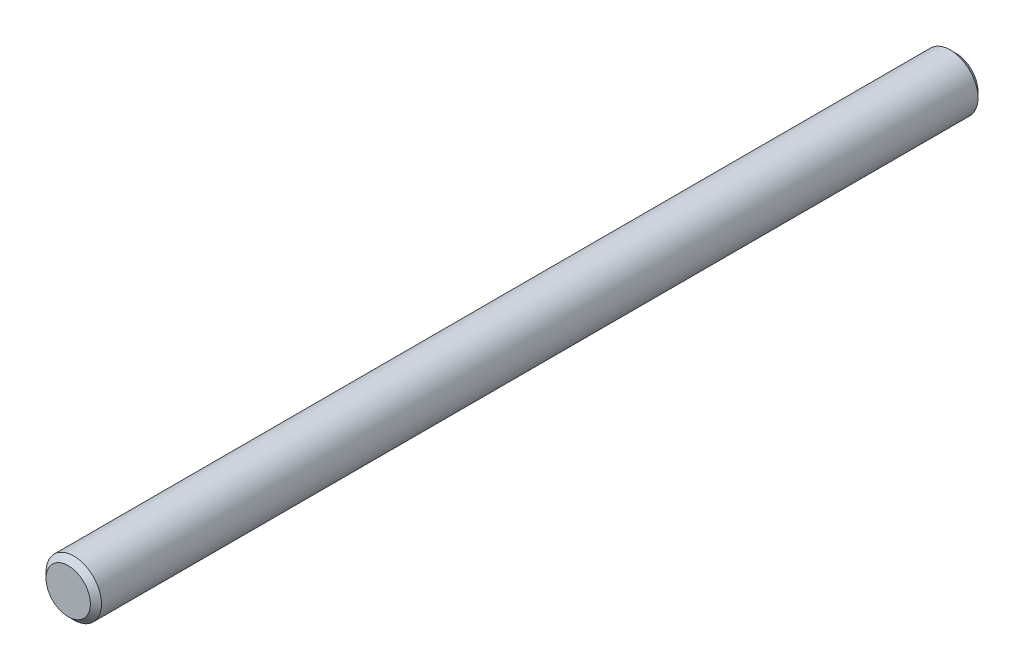
SolidWorks part; units mm, degrees
material "Plain Carbon Steel"
ref_plane "Front" through (0, 0, 0) normal (0, 0, 1) x (1, 0, 0)
ref_plane "Top" through (0, 0, 0) normal (0, 1, 0) x (1, 0, 0)
ref_plane "Right" through (0, 0, 0) normal (1, 0, 0) x (0, 0, -1)
sketch "Sketch1" plane through (0, 0, 0) normal (0, 0, 1) x (1, 0, 0)
  circle A0 centre (0, 0) radius 1.5875
  dimension "dia" = 3.175
sketch "Sketch2" plane through (0, 0, 0) normal (1, 0, 0) x (0, 0, -1)
  line L0 (-25.4, 0) -> (25.4, 0) construction
  line L1 (1.7463, 0) -> (-1.7463, 0) construction
  line L3 (25.4, 1.5875) -> (25.4, -1.5875) construction
  line L4 (-25.4, 1.5875) -> (-25.4, -1.5875) construction
  line L5 (-6.35, 1.5875) -> (-6.35, -1.5875) construction
  line L6 (6.35, 1.5875) -> (6.35, -1.5875) construction
  point P6 (0, 0)
  point P10 (25.4, 0)
  point P13 (-25.4, 0)
  point P16 (-6.35, 0)
  point P19 (6.35, 0)
  dimension "D1" = 3.175
  dimension "lg" = 50.8
  dimension "D2" = 19.05
  dimension "D3" = 19.05
sketch "Sketch3" plane through (0, 0, 0) normal (0, 0, 1) x (1, 0, 0)
  line L0 (0, 1.5875) -> (0, -1.5875) construction
  circle A0 centre (0, 0) radius 1.5875
  dimension "D1" = 3.175
extrude "Boss-Extrude1" add sketch "Sketch3" along normal mid plane 50.8
chamfer "Chamfer1" distance 0.3175 angle 45 2 edges at (1.5875, 0, -25.4) (1.5875, 0, 25.4)
equation "\"D1@Sketch2\"=\"dia@sketch1\""
equation "\"D1@Sketch3\"=\"dia@Sketch1\""
equation "\"D1@Boss-Extrude1\"=\"lg@Sketch2\""
equation "\"D1@Chamfer1\"=\"dia@Sketch1\"*.1"
